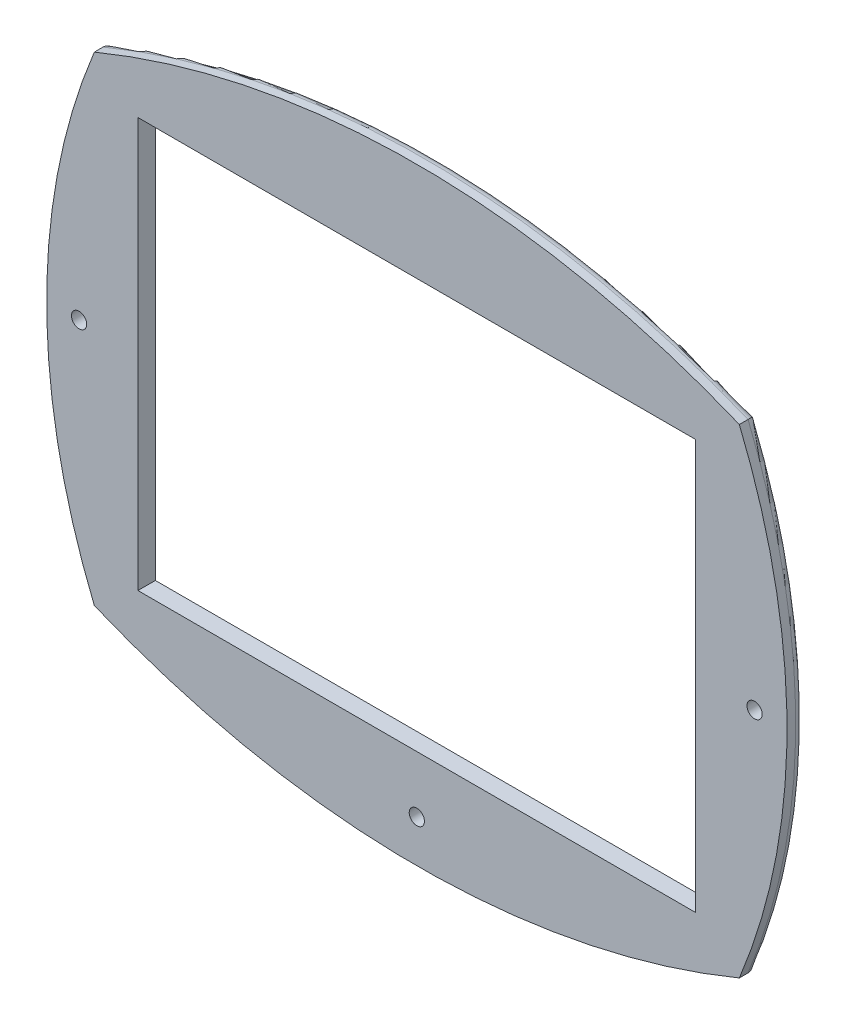
SolidWorks part; units mm, degrees
ref_plane "Front Plane" through (0, 0, 0) normal (0, 0, 1) x (1, 0, 0)
ref_plane "Top Plane" through (0, 0, 0) normal (0, 1, 0) x (1, 0, 0)
ref_plane "Right Plane" through (0, 0, 0) normal (1, 0, 0) x (0, 0, -1)
sketch "Sketch1" plane through (0, 0, 0) normal (0, 0, 1) x (1, 0, 0)
  line L1 (0, 34.8598) -> (0, -34.8598) construction
  line L2 (-32, 23.5) -> (32, 23.5)
  line L3 (-32, 23.5) -> (-32, -23.5)
  line L4 (-32, -23.5) -> (32, -23.5)
  line L5 (32, 23.5) -> (32, -23.5)
  line L6 (-32, 23.5) -> (32, -23.5) construction
  line L7 (-32, -23.5) -> (32, 23.5) construction
  arc A0 (-37, 27.5) -> (37, 27.5) centre (0, -61.8259) cw
  arc A1 (-37, 27.5) -> (-37, -27.5) centre (29.3909, 0) ccw
  arc A2 (-37, -27.5) -> (37, -27.5) centre (0, 61.8259) ccw
  arc A3 (37, 27.5) -> (37, -27.5) centre (-29.3909, 0) cw
  arc A4 (36, -25.5) -> (-36, -25.5) centre (0, 65.6482) cw
  arc A5 (-36, 25.5) -> (-36, -25.5) centre (34.5319, 0) ccw
  arc A6 (-36, 25.5) -> (36, 25.5) centre (0, -65.6482) cw
  arc A7 (36, -25.5) -> (36, 25.5) centre (-34.5319, 0) ccw
  point P1 (-37, -27.5)
  point P2 (37, -27.5)
  point P3 (-37, 27.5)
  point P4 (37, 27.5)
  point P5 (0, 0)
  point P15 (-42.4701, 0)
  point P16 (42.4701, 0)
  point P17 (0, -34.8598)
  point P18 (0, 34.8598)
  point P19 (0, 0)
  dimension "D5" = 47
  dimension "D1" = 72
  dimension "D2" = 51
  dimension "D3" = 55
  dimension "D4" = 74
  dimension "D6" = 64
extrude "Boss-Extrude1" add sketch "Sketch1" along normal blind 2 contours A4 A7 A6 A5 L2 L5 L4 L3 | A3 A0 A1 A2 A7 A4 A5 A6 region at (0, 33.7609, 0) region at (0, -31.3156, 0)
fillet "Fillet1" radius 1 4 edges at (-42.4701, 0, 0) (0, -34.8598, 0) (42.4701, 0, 0) (0, 34.8598, 0)
sketch "Sketch2" plane through (0, 0, 0) normal (0, 0, -1) x (-1, 0, 0)
  line L0 (32, 23.5) -> (32, -23.5) construction
  line L1 (-32, 23.5) -> (-32, -23.5) construction
  line L2 (32, -23.5) -> (-32, -23.5) construction
  circle A0 centre (-38.75, 0) radius 0.875
  circle A1 centre (0, -30) radius 0.875
  circle A2 centre (38.75, 0) radius 0.875
  arc A3 (36.2335, -26.7341) -> (36.2335, 26.7341) centre (-29.3909, 0) ccw construction
  arc A4 (-36.2335, 26.7341) -> (-36.2335, -26.7341) centre (29.3909, 0) ccw construction
  point P6 (41.4701, 0)
  point P10 (-41.4701, 0)
  dimension "D1" = 6.75
  dimension "D3" = 1.75
  dimension "D4" = 1.75
  dimension "D5" = 1.75
  dimension "D2" = 6.75
  dimension "D6" = 6.5
extrude "Cut-Extrude1" cut sketch "Sketch2" against normal through all
